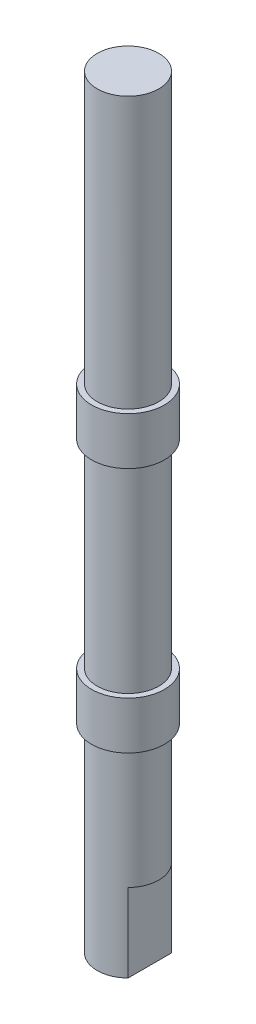
SolidWorks part; units mm, degrees
ref_plane "前视基准面" through (0, 0, 0) normal (0, 0, 1) x (1, 0, 0)
ref_plane "上视基准面" through (0, 0, 0) normal (0, 1, 0) x (1, 0, 0)
ref_plane "右视基准面" through (0, 0, 0) normal (1, 0, 0) x (0, 0, -1)
sketch "草图1" plane through (0, 0, 0) normal (0, 1, 0) x (1, 0, 0)
  circle A0 centre (0, 0) radius 2.75
  dimension "D1" = 5.5
extrude "凸台-拉伸1" add sketch "草图1" along normal blind 61.2
sketch "草图2" plane through (0, 0, 0) normal (0, -1, 0) x (1, 0, 0)
  line L0 (0, 0) -> (0, -4.8851) construction
  line L2 (-1.95, 1.9391) -> (-1.95, -1.9391)
  line L4 (1.95, 1.9391) -> (1.95, -1.9391)
  arc A0 (-1.95, -1.9391) -> (1.95, -1.9391) centre (0, 0) ccw
  arc A1 (1.95, 1.9391) -> (-1.95, 1.9391) centre (0, 0) ccw
  dimension "D1" = 5.5
  dimension "D2" = 3.9
extrude "凸台-拉伸2" add sketch "草图2" along normal blind 7
sketch "草图3" plane through (0, -7, 0) normal (0, -1, 0) x (1, 0, 0)
  circle A0 centre (0, 0) radius 3.25
  dimension "D1" = 6.5
extrude "凸台-拉伸3" add sketch "草图3" along normal blind 4.25 from offset 22 offset against normal yes
extrude "凸台-拉伸4" add sketch "草图3<2>" along normal blind 4.25 from offset 44 offset against normal yes
sketch "草图3<2>" plane through (0, -7, 0) normal (0, -1, 0) x (1, 0, 0) same geometry as "草图3"
